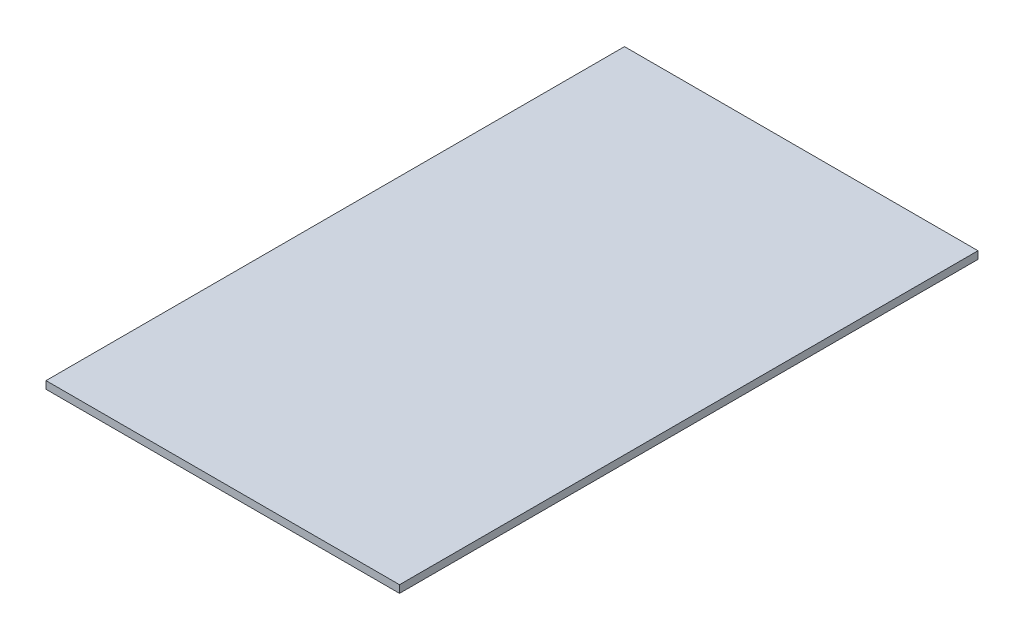
SolidWorks part; units mm, degrees
ref_plane "Front Plane" through (0, 0, 0) normal (0, 0, 1) x (1, 0, 0)
ref_plane "Top Plane" through (0, 0, 0) normal (0, 1, 0) x (1, 0, 0)
ref_plane "Right Plane" through (0, 0, 0) normal (1, 0, 0) x (0, 0, -1)
sketch "Sketch1" plane through (0, 0, 0) normal (0, 1, 0) x (1, 0, 0)
  line L1 (-279.4, -457.2) -> (279.4, -457.2)
  line L2 (-279.4, -457.2) -> (-279.4, 457.2)
  line L3 (-279.4, 457.2) -> (279.4, 457.2)
  line L4 (279.4, -457.2) -> (279.4, 457.2)
  line L5 (-279.4, -457.2) -> (279.4, 457.2) construction
  line L6 (-279.4, 457.2) -> (279.4, -457.2) construction
  point P0 (0, 0)
  dimension "D1" = 558.8
  dimension "D2" = 914.4
extrude "Boss-Extrude1" add sketch "Sketch1" along normal blind 11.9062
